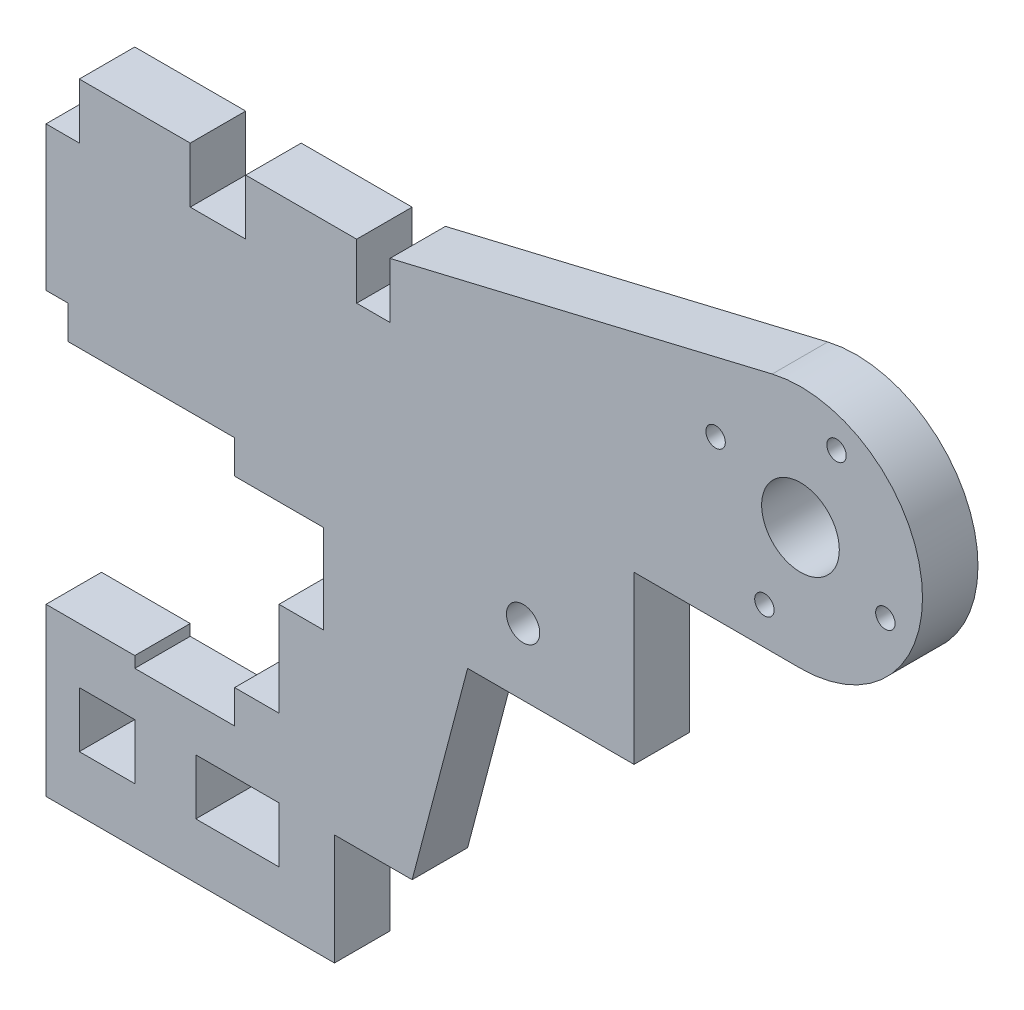
SolidWorks part; units mm, degrees
ref_plane "Plan de face" through (0, 0, 0) normal (0, 0, 1) x (1, 0, 0)
ref_plane "Plan de dessus" through (0, 0, 0) normal (0, 1, 0) x (1, 0, 0)
ref_plane "Plan de droite" through (0, 0, 0) normal (1, 0, 0) x (0, 0, -1)
sketch "Esquisse1" plane through (0, 0, 0) normal (0, 0, 1) x (1, 0, 0)
  line L0 (-8, -10) -> (18, -10)
  line L1 (18, 0) -> (18, -10)
  line L2 (0, 5) -> (0, 4)
  line L3 (5, 42.5) -> (10, 42.5)
  line L4 (56.75, 37.35) -> (63.25, 52.65) construction
  line L5 (20, 42.5) -> (23, 42.5)
  line L6 (-5, 42.5) -> (-5, 47.5)
  line L7 (-5, 47.5) -> (5, 47.5)
  line L8 (5, 42.5) -> (5, 47.5)
  line L9 (18, 0) -> (25, 0)
  line L10 (10, 42.5) -> (10, 47.5)
  line L11 (10, 47.5) -> (20, 47.5)
  line L12 (20, 42.5) -> (20, 47.5)
  line L13 (60, 34) -> (45, 34)
  line L14 (13, 0) -> (5.5, 0)
  line L15 (13, 0) -> (13, -5)
  line L16 (13, -5) -> (5.5, -5)
  line L17 (5.5, 0) -> (5.5, -5)
  line L18 (0, 0) -> (-5, 0)
  line L19 (-6, 29.5) -> (-6, 26.5)
  line L20 (0, 4) -> (9, 4)
  line L21 (60, 45) -> (52.35, 45) construction
  line L22 (-6, 26.5) -> (9, 26.5)
  line L23 (17, 15.5) -> (17, 23.5)
  line L24 (0, 0) -> (0, -5)
  line L25 (0, 0) -> (0, 5)
  line L26 (0, 5) -> (-8, 5)
  line L27 (-8, -10) -> (-8, 5)
  line L28 (-5, 42.5) -> (-8, 42.5)
  line L29 (0, -5) -> (-5, -5)
  line L30 (-6, 29.5) -> (-8, 29.5)
  line L31 (-8, 42.5) -> (-8, 29.5)
  line L32 (17, 23.5) -> (9, 23.5)
  line L33 (52.35, 45) -> (52.35, 48.25) construction
  line L34 (9, 7) -> (13, 7)
  line L35 (9, 23.5) -> (9, 26.5)
  line L36 (17, 15.5) -> (13, 15.5)
  line L37 (67.65, 41.75) -> (52.35, 48.25) construction
  line L38 (30, 19) -> (25, 0)
  line L39 (9, 7) -> (9, 4)
  line L40 (-5, 0) -> (-5, -5)
  line L41 (13, 7) -> (13, 15.5)
  line L42 (57.4528, 55.701) -> (23, 47.5)
  line L43 (45, 19) -> (45, 34)
  line L46 (23, 42.5) -> (23, 47.5)
  line L48 (45, 19) -> (30, 19)
  circle A0 centre (35, 25) radius 1.5
  circle A1 centre (60, 45) radius 3.5
  arc A2 (60, 34) -> (57.4528, 55.701) centre (60, 45) ccw
  circle A3 centre (52.35, 45) radius 0.875 construction
  circle A4 centre (52.35, 48.25) radius 0.875
  circle A5 centre (63.25, 52.65) radius 0.875
  circle A6 centre (67.65, 41.75) radius 0.875
  circle A7 centre (56.75, 37.35) radius 0.875
  point P56 (60, 45)
  dimension "D18" = 7
  dimension "D19" = 3
  dimension "D25" = 3.25
  dimension "D27" = 11
  dimension "D28" = 1.75
  dimension "D24" = 7
  dimension "D3" = 10
  dimension "D4" = 5
  dimension "D5" = 5
  dimension "D6" = 8
  dimension "D7" = 15
  dimension "D8" = 2
  dimension "D9" = 16
  dimension "D10" = 3
  dimension "D11" = 3
  dimension "D12" = 4
  dimension "D13" = 10
  dimension "D14" = 3
  dimension "D15" = 8
  dimension "D16" = 8
  dimension "D17" = 8
  dimension "D20" = 20
  dimension "D21" = 2.5
  dimension "D22" = 17
  dimension "D23" = 25
  dimension "D26" = 7.65
  dimension "D30" = 4
  dimension "D31" = 3
  dimension "D32" = 1
  dimension "D34" = 42.5
  dimension "D35" = 26
  dimension "D36" = 5
  dimension "D37" = 5
  dimension "D38" = 7.5
  dimension "D39" = 5
  dimension "D40" = 104.744
  dimension "D41" = 3
  dimension "D42" = 6
  dimension "D43" = 15
  dimension "D29" = 4
extrude "Boss.-Extru.1" add sketch "Esquisse1" along normal blind 5 contours L5 L12 L11 L10 L3 L8 L7 L6 | L28 L31 L30 | L19 L22 L23 L20 L2 L25 L9 | L27 L25 L26 region at (26.0938, 29.0475, 0)
